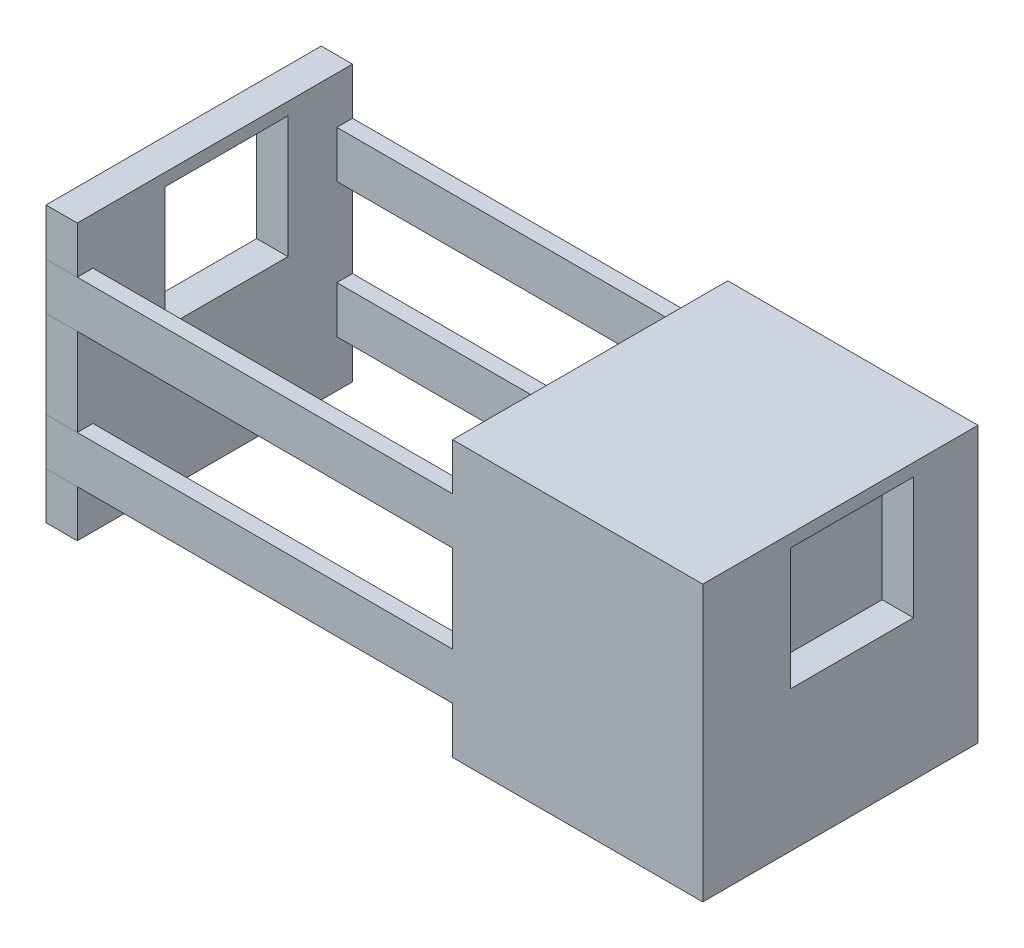
SolidWorks part; units mm, degrees
ref_plane "Front Plane" through (0, 0, 0) normal (0, 0, 1) x (1, 0, 0)
ref_plane "Top Plane" through (0, 0, 0) normal (0, 1, 0) x (1, 0, 0)
ref_plane "Right Plane" through (0, 0, 0) normal (1, 0, 0) x (0, 0, -1)
sketch "Sketch1" plane through (0, 0, 0) normal (1, 0, 0) x (0, 0, -1)
  line L1 (0, 0) -> (22.352, 0)
  line L2 (0, 0) -> (0, 22.352)
  line L3 (0, 22.352) -> (22.352, 22.352)
  line L4 (22.352, 0) -> (22.352, 22.352)
  dimension "D1" = 22.352
  dimension "D2" = 22.352
extrude "Boss-Extrude1" add sketch "Sketch1" along normal blind 2.54
pattern_linear "LPattern1" count 2 spacing 50.8 along (-1, 0, 0) of bodies 101
sketch "Sketch2" plane through (2.54, 0, 0) normal (1, 0, 0) x (0, 0, -1)
  line L0 (0, 0) -> (22.352, 0) construction
  line L1 (7.112, 21.336) -> (17.112, 21.336)
  line L2 (7.112, 21.336) -> (7.112, 11.43)
  line L3 (7.112, 11.43) -> (17.112, 11.43)
  line L4 (17.112, 21.336) -> (17.112, 11.43)
  line L5 (0, 22.352) -> (0, 0) construction
  line L9 (11.176, 22.352) -> (11.176, 0) construction
  line L14 (22.352, 22.352) -> (0, 22.352) construction
  line L15 (0, 11.176) -> (22.352, 11.176) construction
  line L29 (0, 18.542) -> (1.27, 18.542)
  line L30 (0, 18.542) -> (0, 14.732)
  line L31 (0, 14.732) -> (1.27, 14.732)
  line L32 (1.27, 18.542) -> (1.27, 14.732)
  line L33 (22.352, 0) -> (22.352, 22.352) construction
  line L34 (22.352, 14.732) -> (21.082, 14.732)
  line L35 (21.082, 18.542) -> (21.082, 14.732)
  line L36 (22.352, 18.542) -> (21.082, 18.542)
  line L37 (22.352, 18.542) -> (22.352, 14.732)
  line L38 (22.352, 3.81) -> (22.352, 7.62)
  line L39 (22.352, 3.81) -> (21.082, 3.81)
  line L40 (21.082, 3.81) -> (21.082, 7.62)
  line L41 (22.352, 7.62) -> (21.082, 7.62)
  line L42 (0, 7.62) -> (1.27, 7.62)
  line L43 (1.27, 3.81) -> (1.27, 7.62)
  line L44 (0, 3.81) -> (1.27, 3.81)
  line L45 (0, 3.81) -> (0, 7.62)
  dimension "D1" = 11.43
  dimension "D2" = 10
  dimension "D3" = 7.112
  dimension "D5" = 3.81
  dimension "D6" = 1.27
  dimension "D7" = 7.62
  dimension "D4" = 9.906
extrude "Cut-Extrude1" cut sketch "Sketch2" against normal through all
sketch "Sketch3" plane through (2.54, 0, 0) normal (1, 0, 0) x (0, 0, -1)
  line L1 (0, 18.542) -> (1.27, 18.542)
  line L2 (0, 18.542) -> (0, 14.732)
  line L3 (0, 14.732) -> (1.27, 14.732)
  line L4 (1.27, 18.542) -> (1.27, 14.732)
  line L5 (21.082, 18.542) -> (22.352, 18.542)
  line L6 (21.082, 18.542) -> (21.082, 14.732)
  line L7 (21.082, 14.732) -> (22.352, 14.732)
  line L8 (22.352, 18.542) -> (22.352, 14.732)
  line L9 (21.082, 7.62) -> (22.352, 7.62)
  line L10 (21.082, 7.62) -> (21.082, 3.81)
  line L11 (21.082, 3.81) -> (22.352, 3.81)
  line L12 (22.352, 7.62) -> (22.352, 3.81)
  line L13 (0, 7.62) -> (1.27, 7.62)
  line L14 (0, 7.62) -> (0, 3.81)
  line L15 (0, 3.81) -> (1.27, 3.81)
  line L16 (1.27, 7.62) -> (1.27, 3.81)
  line L17 (1.27, 18.542) -> (0, 18.542)
  line L18 (1.27, 18.542) -> (1.27, 14.732)
  line L19 (1.27, 14.732) -> (0, 14.732)
  line L20 (0, 18.542) -> (0, 14.732)
  line L21 (22.352, 18.542) -> (21.082, 18.542)
  line L22 (22.352, 18.542) -> (22.352, 14.732)
  line L23 (22.352, 14.732) -> (21.082, 14.732)
  line L24 (21.082, 18.542) -> (21.082, 14.732)
  line L25 (22.352, 7.62) -> (21.082, 7.62)
  line L26 (22.352, 7.62) -> (22.352, 3.81)
  line L27 (22.352, 3.81) -> (21.082, 3.81)
  line L28 (21.082, 7.62) -> (21.082, 3.81)
  line L29 (1.27, 7.62) -> (0, 7.62)
  line L30 (1.27, 7.62) -> (1.27, 3.81)
  line L31 (1.27, 3.81) -> (0, 3.81)
  line L32 (0, 7.62) -> (0, 3.81)
  line M6 (0, 18.542) -> (1.27, 18.542)
  line M7 (1.27, 18.542) -> (1.27, 14.732)
  line M8 (1.27, 14.732) -> (0, 14.732)
  line M10 (0, 7.62) -> (1.27, 7.62)
  line M11 (1.27, 7.62) -> (1.27, 3.81)
  line M12 (1.27, 3.81) -> (0, 3.81)
  line M16 (22.352, 3.81) -> (21.082, 3.81)
  line M17 (21.082, 3.81) -> (21.082, 7.62)
  line M18 (21.082, 7.62) -> (22.352, 7.62)
  line M20 (22.352, 14.732) -> (21.082, 14.732)
  line M21 (21.082, 14.732) -> (21.082, 18.542)
  line M22 (21.082, 18.542) -> (22.352, 18.542)
extrude "Boss-Extrude2" add sketch "Sketch3" against normal up to surface (53.34 mm away) separate body contours L2 M6 M8 M7 | L14 M10 M12 M11 | L8 M22 M21 M20 | L12 M18 M17 M16 region at (2.54, 16.637, -0.635) region at (2.54, 16.637, -21.717) region at (2.54, 5.715, -21.717) region at (2.54, 5.715, -0.635) up to face at (-50.8, 16.383, -12.112)
sketch "Sketch5" plane through (2.54, 0, 0) normal (1, 0, 0) x (0, 0, -1)
  line L0 (7.112, 11.43) -> (17.112, 11.43) construction
  line L1 (6.308, 13.462) -> (2.5432, 13.462)
  line L2 (6.308, 13.462) -> (6.308, 17.0327)
  line L3 (6.308, 17.0327) -> (2.5432, 17.0327)
  line L4 (2.5432, 13.462) -> (2.5432, 17.0327)
  dimension "D1" = 2.032
sketch "Sketch7" plane through (0, 0, 0) normal (-1, 0, 0) x (0, 0, 1)
  line L20 (-1.27, 18.542) -> (0, 18.542)
  line L21 (0, 18.542) -> (0, 22.352)
  line L22 (0, 22.352) -> (-22.352, 22.352)
  line L23 (-22.352, 22.352) -> (-22.352, 18.542)
  line L24 (-22.352, 18.542) -> (-21.082, 18.542)
  line L25 (-21.082, 18.542) -> (-21.082, 14.732)
  line L26 (-21.082, 14.732) -> (-22.352, 14.732)
  line L27 (-22.352, 14.732) -> (-22.352, 7.62)
  line L28 (-22.352, 7.62) -> (-21.082, 7.62)
  line L29 (-21.082, 7.62) -> (-21.082, 3.81)
  line L30 (-21.082, 3.81) -> (-22.352, 3.81)
  line L31 (-22.352, 3.81) -> (-22.352, 0)
  line L32 (-22.352, 0) -> (0, 0)
  line L33 (0, 0) -> (0, 3.81)
  line L34 (0, 3.81) -> (-1.27, 3.81)
  line L35 (-1.27, 3.81) -> (-1.27, 7.62)
  line L36 (-1.27, 7.62) -> (0, 7.62)
  line L37 (0, 7.62) -> (0, 14.732)
  line L38 (0, 14.732) -> (-1.27, 14.732)
  line L39 (-1.27, 14.732) -> (-1.27, 18.542)
  line L40 (-1.27, 18.542) -> (0, 18.542)
  line L41 (0, 18.542) -> (0, 22.352)
  line L42 (0, 22.352) -> (-22.352, 22.352)
  line L43 (-22.352, 22.352) -> (-22.352, 18.542)
  line L44 (-22.352, 18.542) -> (-21.082, 18.542)
  line L45 (-21.082, 18.542) -> (-21.082, 14.732)
  line L46 (-21.082, 14.732) -> (-22.352, 14.732)
  line L47 (-22.352, 14.732) -> (-22.352, 7.62)
  line L48 (-22.352, 7.62) -> (-21.082, 7.62)
  line L49 (-21.082, 7.62) -> (-21.082, 3.81)
  line L50 (-21.082, 3.81) -> (-22.352, 3.81)
  line L51 (-22.352, 3.81) -> (-22.352, 0)
  line L52 (-22.352, 0) -> (0, 0)
  line L53 (0, 0) -> (0, 3.81)
  line L54 (0, 3.81) -> (-1.27, 3.81)
  line L55 (-1.27, 3.81) -> (-1.27, 7.62)
  line L56 (-1.27, 7.62) -> (0, 7.62)
  line L57 (0, 7.62) -> (0, 14.732)
  line L58 (0, 14.732) -> (-1.27, 14.732)
  line L59 (-1.27, 14.732) -> (-1.27, 18.542)
  dimension "D1" = 0
extrude "Boss-Extrude3" add sketch "Sketch7" along normal blind 17.78
equation "\"Stupid\" = 3 * 2"
equation "\"shaft entry\"=0.393701"
equation "\"D2@Sketch2\"=\"shaft entry\""
